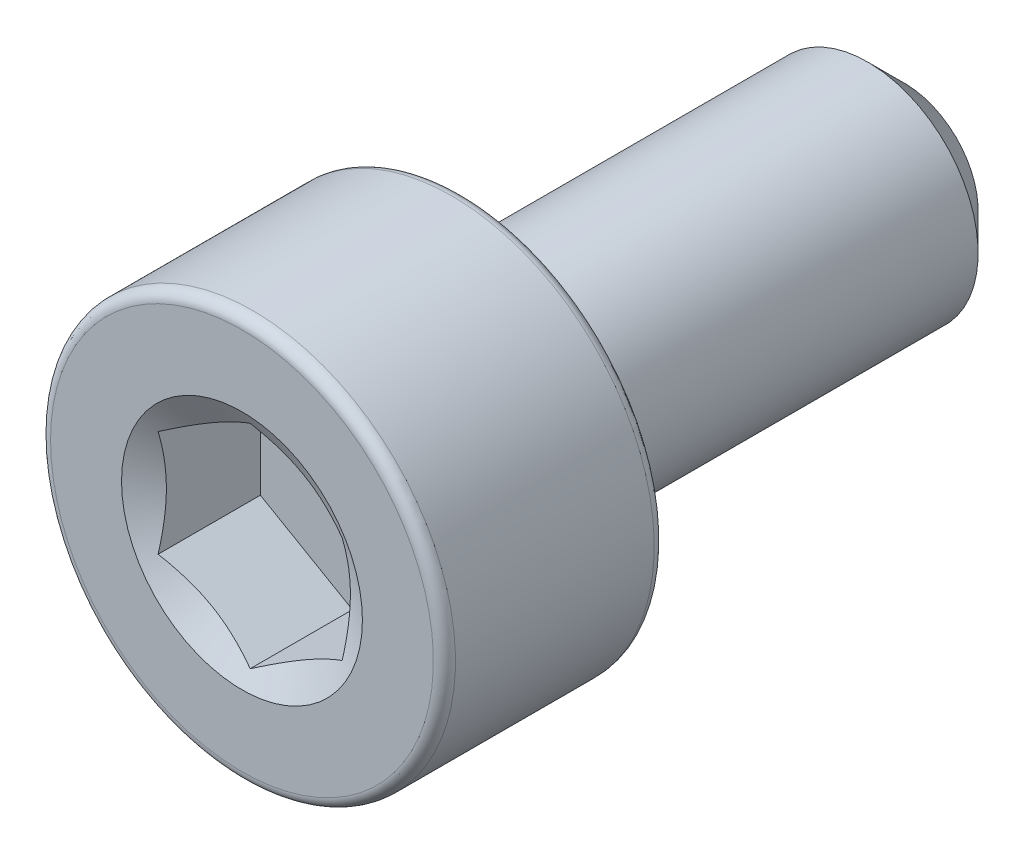
SolidWorks part; units mm, degrees
ref_plane "Front Plane" through (0, 0, 0) normal (0, 0, 1) x (1, 0, 0)
ref_plane "Top Plane" through (0, 0, 0) normal (0, 1, 0) x (1, 0, 0)
ref_plane "Right Plane" through (0, 0, 0) normal (1, 0, 0) x (0, 0, -1)
sketch "Sketch1" plane through (0, 0, 0) normal (1, 0, 0) x (0, 0, -1)
  line L0 (4.5, 0) -> (-4.5, 0) construction
  line L1 (-1.5, 2.75) -> (-1.5, -2.75) construction
  line L2 (4.5, 1.5) -> (4.5, -1.5) construction
  line L3 (4.4688, 1.5541) -> (4.7188, 1.1211) construction
  line L4 (4.6875, 1.1752) -> (4.75, 1.1752) construction
  line L5 (4.7188, 1.1211) -> (4.9688, 1.5541) construction
  line L6 (4.9688, 1.5541) -> (4.4688, 1.5541) construction
  line L7 (4.7188, 1.1752) -> (4.7188, 1.1211) construction
  line L8 (4.7188, 1.5541) -> (4.7188, 1.5) construction
  line L9 (4.9375, 1.5) -> (4.5, 1.5) construction
  point P4 (-1.5, 0)
  point P6 (-1.5, 1.25)
  point P7 (3.25, -1.5)
  point P20 (4.7188, 1.5271)
  dimension "Head Height" = 3
  dimension "Head Diameter" = 5.5
  dimension "Drive Size" = 2.5
  dimension "Length" = 6
  dimension "Thread Size" = 3
  dimension "Thread Pitch" = 0.5
  dimension "Pitch/8" = 0.0625
  dimension "Thread Note" = 1.25
sketch "Sketch2" plane through (0, 0, 0) normal (1, 0, 0) x (0, 0, -1)
  line L0 (4.5, 0) -> (4.5, 1)
  line L1 (4.5, 1.5) -> (4.5, -1.5) construction
  line L2 (4.5, 1) -> (4, 1.5)
  line L3 (4, 1.5) -> (-1.5, 1.5)
  line L4 (-1.5, 1.5) -> (-1.5, 2.6)
  line L5 (-1.65, 2.75) -> (-4.35, 2.75)
  line L6 (-4.5, 2.6) -> (-4.5, 0)
  line L7 (4.5, 0) -> (-4.5, 0) construction
  line L8 (-4.5, 0) -> (4.5, 0)
  arc A0 (-1.5, 2.6) -> (-1.65, 2.75) centre (-1.65, 2.6) ccw
  arc A1 (-4.35, 2.75) -> (-4.5, 2.6) centre (-4.35, 2.6) ccw
  point P19 (-1.5, 2.75)
  dimension "D3" = 0.15
  dimension "D1" = 0.5
  dimension "D2" = 45
revolve "Revolve1" add sketch "Sketch2" angle 360 about L0
sketch "Sketch3" plane through (0, 0, 0) normal (0, 0, 1) x (1, 0, 0)
  line L1 (-1.25, 0.7217) -> (-1.25, -0.7217)
  line L2 (-1.25, -0.7217) -> (0, -1.4434)
  line L3 (0, -1.4434) -> (1.25, -0.7217)
  line L4 (1.25, -0.7217) -> (1.25, 0.7217)
  line L5 (1.25, 0.7217) -> (0, 1.4434)
  line L6 (0, 1.4434) -> (-1.25, 0.7217)
  circle A0 centre (0, 0) radius 1.25 construction
  circle A1 centre (0, 0) radius 2.75 construction
extrude "Cut-Extrude1" cut sketch "Sketch3" against normal blind 1.5 from vertex starting at point (0, 0, 4.5)
sketch "Sketch4" plane through (0, 0, 4.5) normal (0, 0, 1) x (1, 0, 0)
  line L0 (0, 1.4434) -> (0, 1.8289) construction
  line L1 (0, 1.8289) -> (0, 2.2145) construction
  line L2 (0, 2.2145) -> (0, 2.6) construction
  circle A0 centre (0, 0) radius 1.6361
  point P12 (0, 1.6361)
extrude "Cut-Extrude2" cut sketch "Sketch4" against normal through all draft 60
split "Split1" [suppressed] bodies to split 106 112
sketch "Sketch5" [suppressed] plane through (0, 0, 0) normal (1, 0, 0) x (0, 0, -1)
  line L0 (4.6875, 1.1752) -> (4.75, 1.1752)
  line L1 (4.75, 1.1752) -> (4.9531, 1.5271)
  line L2 (4.9531, 1.5271) -> (4.4844, 1.5271)
  line L3 (4.4844, 1.5271) -> (4.6875, 1.1752)
  line L4 (4.4688, 1.5541) -> (4.7188, 1.1211) construction
sketch "Sketch6" [suppressed] plane through (0, 0, -4.5) normal (0, 0, -1) x (-1, 0, 0)
  circle A0 centre (0, 0) radius 1.5
curve "Helix/Spiral1" [suppressed] pitch 0.5 height 6.5 turns 13
sweep "Cut-Sweep1" [suppressed] cut profiles "Sketch5" path "Helix/Spiral1"
sketch "Sketch7" [suppressed] plane through (0, 0, 1.5) normal (0, 0, -1) x (-1, 0, 0)
  circle A0 centre (0, 0) radius 1.5508
  circle A1 centre (0, 0) radius 1.5 construction
  dimension "D1" = 0.0508
extrude "Boss-Extrude1" [suppressed] add sketch "Sketch7" along normal blind 1.5 draft 20 and the other way blind 0.3
equation "\"Pitch/8@Sketch1\" = \"Thread Pitch@Sketch1\" / 8"
equation "\"Thread Note@Sketch1\" = \"Thread Pitch@Sketch1\" * 2.5"
equation "\"D1@Sketch2\" = \"Thread Pitch@Sketch1\""
equation "\"D3@Sketch2\"=\"Head Height@Sketch1\"*.05"
equation "\"D1@Cut-Extrude1\" = \"Head Height@Sketch1\" * .5"
equation "\"D3@Helix/Spiral1\" = \"Length@Sketch1\" + \"Thread Pitch@Sketch1\""
equation "\"D4@Helix/Spiral1\" = \"Thread Pitch@Sketch1\""
equation "\"D2@Boss-Extrude1\" = \"Head Height@Sketch1\" * .1"
equation "\"D1\"= \"Thread Size@Sketch1\" * .4"
equation "\"D1@Boss-Extrude1\" = \"Thread Pitch@Sketch1\" * 3"
